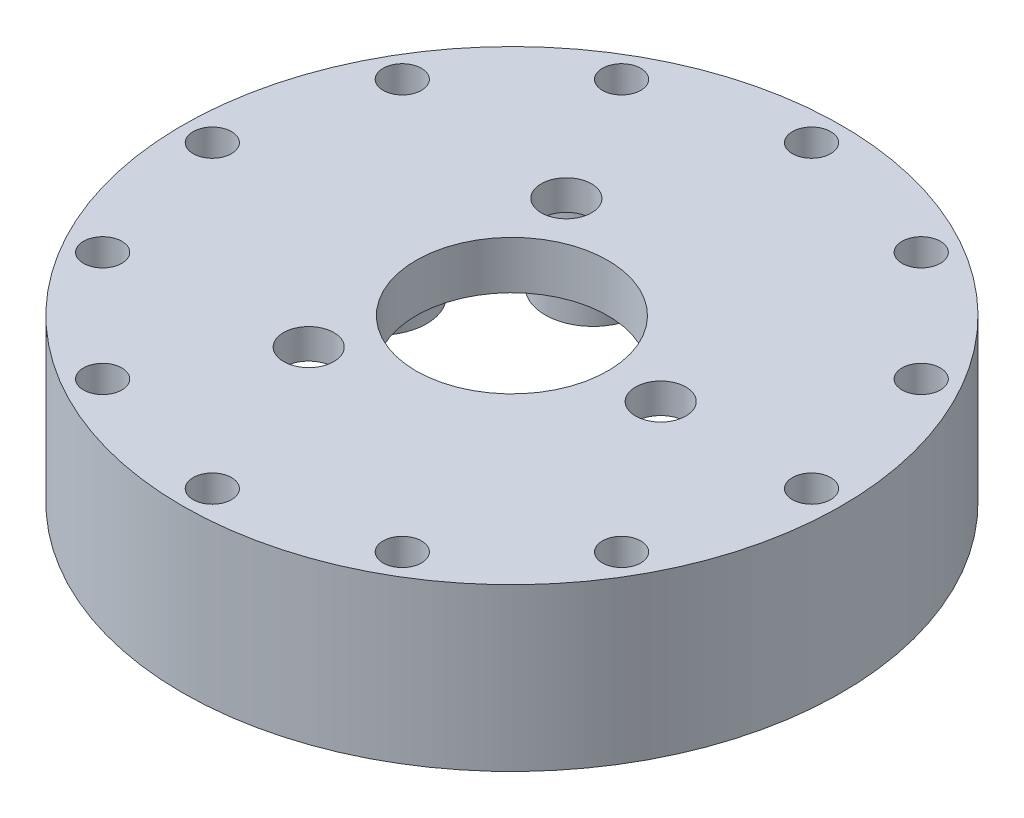
SolidWorks part; units mm, degrees
ref_plane "Front Plane" through (0, 0, 0) normal (0, 0, 1) x (1, 0, 0)
ref_plane "Top Plane" through (0, 0, 0) normal (0, 1, 0) x (1, 0, 0)
ref_plane "Right Plane" through (0, 0, 0) normal (1, 0, 0) x (0, 0, -1)
sketch "Sketch1" plane through (0, 0, 0) normal (0, 1, 0) x (1, 0, 0)
  line L0 (0, 22.5) -> (0, 0) construction
  line L1 (0, 0) -> (12.1644, 18.9282) construction
  line L2 (0, 0) -> (-12.1644, 18.9282) construction
  line L3 (-20.4667, 9.3468) -> (0, 0) construction
  line L4 (0, 0) -> (-22.271, -3.2021) construction
  circle A0 centre (0, 0) radius 22.5
  circle A1 centre (0, 0) radius 27.5
  circle A2 centre (0, 22.5) radius 4
  circle A3 centre (12.1644, 18.9282) radius 4
  circle A4 centre (20.4667, 9.3468) radius 4
  circle A5 centre (22.271, -3.2021) radius 4
  circle A6 centre (17.0044, -14.7344) radius 4
  circle A7 centre (6.339, -21.5886) radius 4
  circle A8 centre (-6.339, -21.5886) radius 4
  circle A9 centre (-17.0044, -14.7344) radius 4
  circle A10 centre (-22.271, -3.2021) radius 4
  circle A11 centre (-20.4667, 9.3468) radius 4
  circle A12 centre (-12.1644, 18.9282) radius 4
  point P27 (0, 0)
  dimension "D1" = 45
  dimension "D2" = 55
  dimension "D3" = 8
  dimension "D4" = 11
extrude "Boss-Extrude2" add sketch "Sketch1" along normal blind 9.5 contours A1 A12 A0 A2 A3 A4 A5 A6 A7 A8 A9 A10 A11 | A0 A11 | A0 A11 | A0 A12 | A0 A12 | A0 A2 | A0 A2 | A0 A3 | A0 A3 | A0 A4 | A0 A4 | A0 A5 | A0 A5 | A0 A6 | A0 A6 | A0 A7 | A0 A7 | A0 A8 | A0 A8 | A0 A9 | A0 A9 | A0 A10 | A0 A10 | A12 region at (20.5288, 0, 2.9516) region at (23.8864, 0, 3.4343) region at (18.8657, 0, -8.6157) region at (21.9512, 0, -10.0248) region at (18.2378, 0, 15.8031) region at (15.6742, 0, 13.5818) region at (11.2128, 0, -17.4475) region at (13.0467, 0, -20.3011) region at (6.7988, 0, 23.1545) region at (5.8431, 0, 19.8998) region at (0, 0, -20.7399) region at (0, 0, -24.132) region at (-6.7988, 0, 23.1545) region at (-5.8431, 0, 19.8998) region at (-11.2128, 0, -17.4475) region at (-13.0467, 0, -20.3011) region at (-18.2378, 0, 15.8031) region at (-15.6742, 0, 13.5818) region at (-18.8657, 0, -8.6157) region at (-21.9512, 0, -10.0248) region at (-23.8864, 0, 3.4343) region at (-20.5288, 0, 2.9516) region at (-26.7222, 0, 0)
sketch "Sketch2" plane through (0, 9.5, 0) normal (0, 1, 0) x (1, 0, 0)
  line L1 (12.413, 0) -> (-6.2065, 10.75) construction
  line L2 (-6.2065, 10.75) -> (-6.2065, -10.75) construction
  line L3 (-6.2065, -10.75) -> (12.413, 0) construction
  circle A0 centre (0, 0) radius 27.5
  circle A1 centre (0, 0) radius 8
  circle A2 centre (0, 0) radius 6.2065 construction
  circle A3 centre (-6.2065, 10.75) radius 2.1
  circle A4 centre (12.413, 0) radius 2.1
  circle A5 centre (-6.2065, -10.75) radius 2.1
  point P16 (0, 0)
  dimension "D1" = 16
  dimension "D2" = 55
  dimension "D4" = 4.2
  dimension "D3" = 21.5
  dimension "D5" = 3
extrude "Boss-Extrude3" add sketch "Sketch2" along normal blind 4
fillet "Fillet2" radius 1 22 edges at (19.3447, 4.75, 11.4905) (10.0616, 4.75, 20.125) (2.416, 4.75, 22.3699) (14.1266, 4.75, 17.5126) (-2.416, 4.75, 22.3699) (-10.0616, 4.75, 20.125) (-14.1266, 4.75, 17.5126) (-19.3447, 4.75, 11.4905) (-21.352, 4.75, 7.0951) (-22.4861, 4.75, -0.7921) (-21.7984, 4.75, -5.575) (-18.4882, 4.75, -12.8233) (-15.3239, 4.75, -16.4751) (-8.6205, 4.75, -20.7831) (-3.9842, 4.75, -22.1444) (3.9842, 4.75, -22.1444) (8.6205, 4.75, -20.7831) (15.3239, 4.75, -16.4751) (18.4882, 4.75, -12.8233) (21.7984, 4.75, -5.575) (22.4861, 4.75, -0.7921) (21.352, 4.75, 7.0951)
sketch "Sketch8" plane through (0, 0, 0) normal (0, -1, 0) x (1, 0, 0)
  circle A0 centre (0, 0) radius 25 construction
  circle A1 centre (0, -25) radius 1.6
  circle A2 centre (-12.5, -21.6506) radius 1.6
  circle A3 centre (-21.6506, -12.5) radius 1.6
  circle A4 centre (-25, 0) radius 1.6
  circle A5 centre (-21.6506, 12.5) radius 1.6
  circle A6 centre (-12.5, 21.6506) radius 1.6
  circle A7 centre (0, 25) radius 1.6
  circle A8 centre (12.5, 21.6506) radius 1.6
  circle A9 centre (21.6506, 12.5) radius 1.6
  circle A10 centre (25, 0) radius 1.6
  circle A11 centre (21.6506, -12.5) radius 1.6
  circle A12 centre (12.5, -21.6506) radius 1.6
  point P30 (0, 0)
  dimension "D1" = 50
  dimension "D2" = 3.2
  dimension "D3" = 12
extrude "Cut-Extrude1" cut sketch "Sketch8" against normal through all
sketch "Sketch9" plane through (0, 9.5, 0) normal (0, -1, 0) x (1, 0, 0)
  circle A0 centre (0, 0) radius 12.413 construction
  circle A1 centre (12.413, 0) radius 4.25
  circle A2 centre (-6.2065, -10.75) radius 4.25
  circle A3 centre (-6.2065, 10.75) radius 4.25
  point P13 (0, 0)
  dimension "D1" = 8.5
  dimension "D2" = 3
extrude "Cut-Extrude2" cut sketch "Sketch9" against normal blind 1.5
